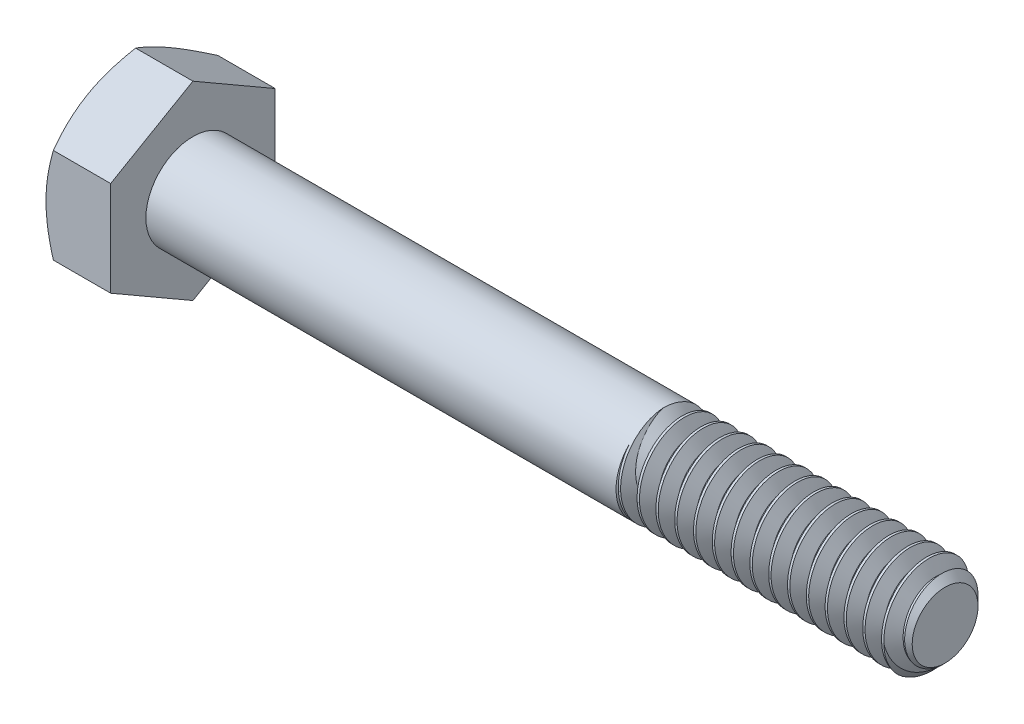
SolidWorks part; units mm, degrees
ref_plane "Front Plane" through (0, 0, 0) normal (0, 0, 1) x (1, 0, 0)
ref_plane "Top Plane" through (0, 0, 0) normal (0, 1, 0) x (1, 0, 0)
ref_plane "Right Plane" through (0, 0, 0) normal (1, 0, 0) x (0, 0, -1)
sketch "Sketch1" plane through (0, 0, 0) normal (0, 0, 1) x (1, 0, 0)
  line L0 (-27.5828, 0) -> (27.5828, 0) construction
  line L1 (27.5828, 3.175) -> (27.5828, -3.175) construction
  line L2 (-23.2172, 5.5562) -> (-23.2172, -5.5562) construction
  line L3 (-27.5828, 5.5562) -> (-27.5828, -5.5562) construction
  point P9 (-23.2172, 0)
  point P10 (23.1378, -3.175)
  dimension "D1" = 4.445
  dimension "Screw Dia" = 6.35
  dimension "Hex" = 11.1125
  dimension "Head Ht" = 4.3656
  dimension "Screw Lenght" = 50.8
ref_plane "Plane2" through (27.5828, 0, 0) normal (1, 0, 0) x (0, 0, -1)
sketch "Sketch5" plane through (27.5828, 0, 0) normal (1, 0, 0) x (0, 0, -1)
  circle A0 centre (0, 0) radius 3.175
extrude "Boss-Extrude3" add sketch "Sketch5" against normal up to vertex (50.8 mm away) up to point (-23.2172, 0, 0)
sketch "Sketch9" plane through (27.5828, 0, 0) normal (1, 0, 0) x (0, 0, -1)
  circle A1 centre (0, 0) radius 3.175
  circle A2 centre (0, 0) radius 3.175
  dimension "D1" = 0
curve "Helix/Spiral1" pitch 1.27 height 20.32 turns 16 parameters "Pitch"=1.27
chamfer "Chamfer1" distance 0.9525 angle 45 1 edges at (27.5828, 0, -3.175)
sketch "Sketch10" plane through (0, 0, 0) normal (0, 0, 1) x (1, 0, 0)
  line L0 (27.5828, 3.175) -> (28.0591, 2.3501)
  line L1 (28.0591, 2.3501) -> (28.2178, 2.3501)
  line L2 (28.2178, 2.3501) -> (28.6941, 3.175)
  line L3 (27.5828, 3.175) -> (28.6941, 3.175)
  line L4 (28.1384, 3.175) -> (28.1384, 2.3501) construction
  line L5 (27.8209, 2.7626) -> (28.4559, 2.7626) construction
  dimension "D1" = 60
  dimension "D2" = 0.1588
  dimension "D3" = 0.635
sweep "Cut-Sweep1" cut profiles "Sketch10" path "Helix/Spiral1" align with end faces yes
sketch "Sketch11" plane through (0, 0, 0) normal (0, 0, 1) x (1, 0, 0)
  line L0 (-23.2172, 3.175) -> (-23.2172, 0)
  line L1 (-23.2172, 0) -> (11.7078, 0)
  line L3 (11.7078, 0) -> (8.5328, 3.175)
  line L4 (-23.2172, 3.175) -> (8.5328, 3.175)
  dimension "D1" = 45
  dimension "MIn Thread" = 19.05
revolve "Revolve1" add sketch "Sketch11" angle 360 about L1
sketch "Sketch6" plane through (-23.2172, 0, 0) normal (-1, 0, 0) x (0, 0, 1)
  line L0 (0, 5.5562) -> (0, -5.5562) construction
  line L1 (5.5562, 3.2079) -> (0, 6.4158)
  line L2 (0, 6.4158) -> (-5.5562, 3.2079)
  line L3 (-5.5562, 3.2079) -> (-5.5562, -3.2079)
  line L4 (-5.5562, -3.2079) -> (0, -6.4158)
  line L5 (0, -6.4158) -> (5.5563, -3.2079)
  line L6 (5.5563, -3.2079) -> (5.5562, 3.2079)
  circle A0 centre (0, 0) radius 5.5562 construction
extrude "Boss-Extrude4" add sketch "Sketch6" along normal up to vertex (4.3656 mm away) up to point (-27.5828, -5.5562, 0)
sketch "Sketch7" plane through (-27.5828, 0, 0) normal (-1, 0, 0) x (0, 0, 1)
  circle A0 centre (0, 0) radius 5.5562 construction
  circle A1 centre (0, 0) radius 5.5562
sketch "Sketch8" plane through (-27.5828, 0, 0) normal (-1, 0, 0) x (0, 0, 1)
  circle A0 centre (0, 0) radius 5.5562 construction
  circle A1 centre (0, 0) radius 5.5562
extrude "Cut-Extrude3" cut sketch "Sketch8" against normal through all draft 60 flip side to cut
sketch "Sketch12" plane through (-27.5828, 0, 0) normal (-1, 0, 0) x (0, 0, 1)
  line L0 (0, 4.2783) -> (0, 2.3892) construction
  line L1 (0.1667, 4.2783) -> (0.1667, 2.3892)
  line L2 (-0.1667, 4.2783) -> (-0.1667, 2.3892)
  line L3 (0, 3.175) -> (0, -3.175) construction
  arc A0 (0.1667, 4.2783) -> (-0.1667, 4.2783) centre (0, 4.2783) ccw
  arc A1 (-0.1667, 2.3892) -> (0.1667, 2.3892) centre (0, 2.3892) ccw
  circle A3 centre (0, 0) radius 2.2225 construction
  circle A4 centre (0, 0) radius 4.445 construction
  point P2 (0, 3.3337)
  dimension "D1" = 4.445
  dimension "D3" = 8.89
  dimension "D2" = 0.3334
extrude "Cut-Extrude4" cut sketch "Sketch12" against normal blind 0.254
pattern_circular "CirPattern1" count 6 over 360 about axis through (0, 0, 0) along (1, 0, 0) of "Cut-Extrude4"
equation "\"D2@Sketch10\" = \"Pitch@Helix/Spiral1\"*.125"
equation "\"D3@Sketch10\" = \"Pitch@Helix/Spiral1\"*.5"
equation "\"D3@Helix/Spiral1\" = \"MIn Thread@Sketch11\"+\"Pitch@Helix/Spiral1\""
equation "\"D1@Chamfer1\" = \"Pitch@Helix/Spiral1\"*.75"
equation "\"D1@Sketch12\" = \"Hex@Sketch1\"*.4"
equation "\"D3@Sketch12\" = \"Hex@Sketch1\"*.8"
equation "\"D2@Sketch12\" = \"Hex@Sketch1\"*.03"
equation "\"D1@Sketch1\" = \"Pitch@Helix/Spiral1\"*3.5"
